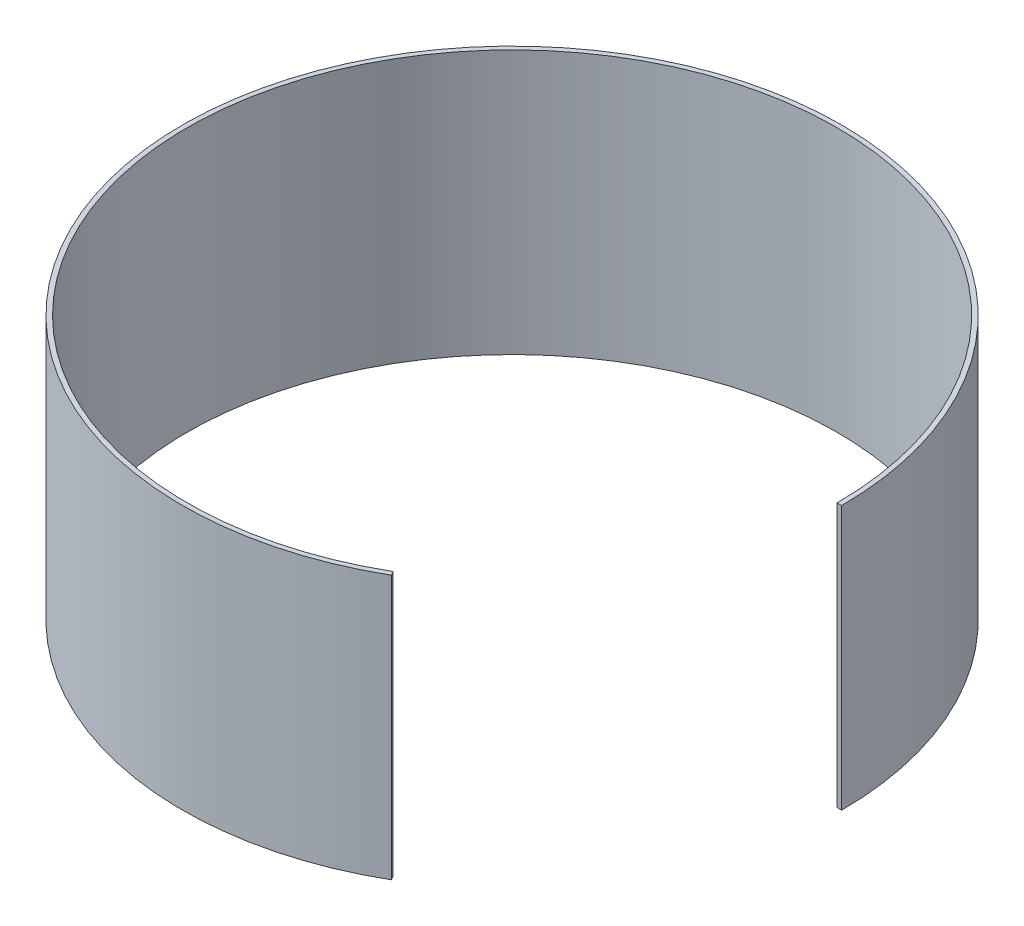
SolidWorks part; units mm, degrees
ref_plane "Front Plane" through (0, 0, 0) normal (0, 0, 1) x (1, 0, 0)
ref_plane "Top Plane" through (0, 0, 0) normal (0, 1, 0) x (1, 0, 0)
ref_plane "Right Plane" through (0, 0, 0) normal (1, 0, 0) x (0, 0, -1)
sketch "Sketch1" plane through (0, 0, 0) normal (0, 0, 1) x (1, 0, 0)
  line L0 (0, 0) -> (0, 158.1672) construction
  line L1 (426, 341) -> (420, 341)
  line L2 (426, 341) -> (426, 0)
  line L3 (426, 0) -> (420, 0)
  line L4 (420, 341) -> (420, 0)
  line L5 (426, 341) -> (420, 0) construction
  line L6 (426, 0) -> (420, 341) construction
  point P0 (423, 170.5)
  dimension "D1" = 6
  dimension "D2" = 420
  dimension "D3" = 341
revolve "Revolve1" add sketch "Sketch1" angle 300 about L0
ref_axis "Axis1" through (0, 341, 0) along (0, -1, 0)
